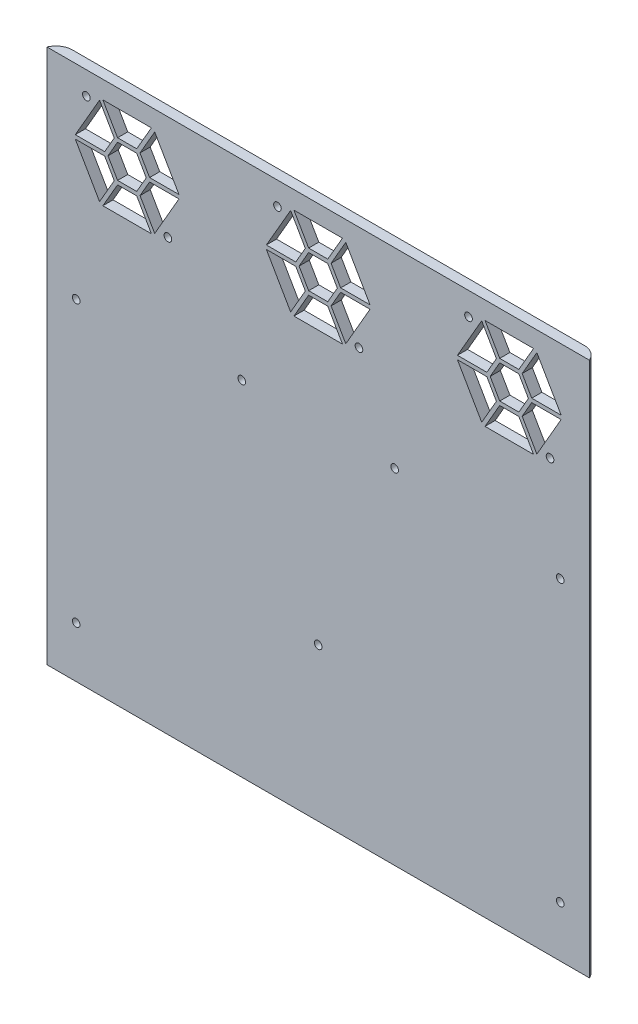
SolidWorks part; units mm, degrees
material "ABS PC"
ref_plane "Plan de face" through (0, 0, 0) normal (0, 0, 1) x (1, 0, 0)
ref_plane "Plan de dessus" through (0, 0, 0) normal (0, 1, 0) x (1, 0, 0)
ref_plane "Plan de droite" through (0, 0, 0) normal (1, 0, 0) x (0, 0, -1)
sketch "Esquisse1" plane through (0, 0, 0) normal (0, 0, 1) x (1, 0, 0)
  line L1 (-106.5, 0) -> (106.5, 0)
  line L2 (-106.5, 0) -> (-106.5, -210)
  line L3 (-106.5, -210) -> (106.5, -210)
  line L4 (106.5, 0) -> (106.5, -210)
  dimension "D1" = 213
  dimension "D2" = 210
extrude "Boss.-Extru.1" add sketch "Esquisse1" along normal blind 4
chamfer "Chanfrein1" distance 4 angle 30 2 edges at (-106.5, -105, 0) (106.5, -105, 0) first distance on face at (-106.5, -105, 2) first distance on face at (106.5, -105, 2)
fillet "Congé1" radius 6.5 2 edges at (-104.1906, -105, 0) (104.1906, -105, 0)
sketch "Esquisse2" plane through (0, 0, 0) normal (0, 0, -1) x (-1, 0, 0)
  line L0 (0, 0) -> (0, -210) construction
  line L1 (-100.4378, 0) -> (100.4378, 0) construction
  line L2 (100.4378, -210) -> (-100.4378, -210) construction
  circle A0 centre (-30, -75) radius 1.5
  circle A1 centre (-95, -80) radius 1.5
  circle A2 centre (-95, -190) radius 1.5
  circle A3 centre (95, -190) radius 1.5
  circle A4 centre (95, -80) radius 1.5
  circle A5 centre (30, -75) radius 1.5
  circle A6 centre (0, -150) radius 1.5
  circle A7 centre (0, -190) radius 1.5 construction
  dimension "D1" = 3
  dimension "D2" = 60
  dimension "D3" = 75
  dimension "D4" = 190
  dimension "D5" = 80
  dimension "D6" = 20
  dimension "D7" = 110
  dimension "D9" = 70
  dimension "D8" = 40
extrude "Enlèv. mat.-Extru.1" cut sketch "Esquisse2" against normal through all
sketch "Esquisse3" plane through (0, 0, 0) normal (0, 0, -1) x (-1, 0, 0)
  line L0 (-75, -6) -> (-75, -44) construction
  line L1 (-100.4378, 0) -> (100.4378, 0) construction
  line L2 (-56, -25) -> (-94, -25) construction
  line L3 (-78.7528, -18.5) -> (-71.2472, -31.5) construction
  line L4 (-67.4944, -25) -> (-71.2472, -18.5)
  line L5 (-71.2472, -18.5) -> (-78.7528, -18.5)
  line L6 (-78.7528, -18.5) -> (-82.5056, -25)
  line L7 (-82.5056, -25) -> (-78.7528, -31.5)
  line L8 (-78.7528, -31.5) -> (-71.2472, -31.5)
  line L9 (-71.2472, -31.5) -> (-67.4944, -25)
  line L10 (-84.5263, -7) -> (-65.4737, -7)
  line L11 (-84.5263, -7) -> (-78.7528, -17)
  line L12 (-78.7528, -17) -> (-71.2472, -17)
  line L13 (-65.4737, -7) -> (-71.2472, -17)
  line L14 (-64.1747, -7.75) -> (-54.6484, -24.25)
  line L15 (-69.9482, -17.75) -> (-66.1954, -24.25)
  line L16 (-54.6484, -24.25) -> (-66.1954, -24.25)
  line L17 (-64.1747, -7.75) -> (-69.9482, -17.75)
  line L18 (-54.6484, -25.75) -> (-64.1747, -42.25)
  line L19 (-66.1954, -25.75) -> (-69.9482, -32.25)
  line L20 (-64.1747, -42.25) -> (-69.9482, -32.25)
  line L21 (-54.6484, -25.75) -> (-66.1954, -25.75)
  line L22 (-65.4737, -43) -> (-84.5263, -43)
  line L23 (-71.2472, -33) -> (-78.7528, -33)
  line L24 (-84.5263, -43) -> (-78.7528, -33)
  line L25 (-65.4737, -43) -> (-71.2472, -33)
  line L26 (-85.8253, -42.25) -> (-95.3516, -25.75)
  line L27 (-80.0518, -32.25) -> (-83.8046, -25.75)
  line L28 (-95.3516, -25.75) -> (-83.8046, -25.75)
  line L29 (-85.8253, -42.25) -> (-80.0518, -32.25)
  line L30 (-95.3516, -24.25) -> (-85.8253, -7.75)
  line L31 (-83.8046, -24.25) -> (-80.0518, -17.75)
  line L32 (-85.8253, -7.75) -> (-80.0518, -17.75)
  line L33 (-95.3516, -24.25) -> (-83.8046, -24.25)
  circle A0 centre (-75, -25) radius 19 construction
  circle A1 centre (-59, -41) radius 1.5 construction
  circle A2 centre (-91, -41) radius 1.5
  circle A3 centre (-91, -9) radius 1.5 construction
  circle A4 centre (-59, -9) radius 1.5
  circle A5 centre (-75, -25) radius 6.5 construction
  point P16 (0, 0)
  point P51 (-75, -25)
  dimension "D1" = 3
  dimension "D2" = 32
  dimension "D3" = 32
  dimension "D4" = 25
  dimension "D5" = 75
  dimension "D6" = 38
  dimension "D7" = 13
  dimension "D8" = 6
  dimension "D9" = 36
  dimension "D10" = 1.5
  dimension "D11" = 1.5
  dimension "D12" = 10
extrude "Enlèv. mat.-Extru.2" cut sketch "Esquisse3" against normal through all
pattern_linear "Répétition linéaire1" count 3 spacing 75 along (-1, 0, 0) of "Enlèv. mat.-Extru.2"
chamfer "Chanfrein2" distance 1.5 angle 45 11 edges at (92.5, -41, 0) (60.5, -9, 0) (17.5, -41, 0) (-14.5, -9, 0) (-57.5, -41, 0) (-89.5, -9, 0) (-93.5, -80, 0) (-93.5, -190, 0) (-1.5, -150, 0) (93.5, -190, 0) (93.5, -80, 0)
